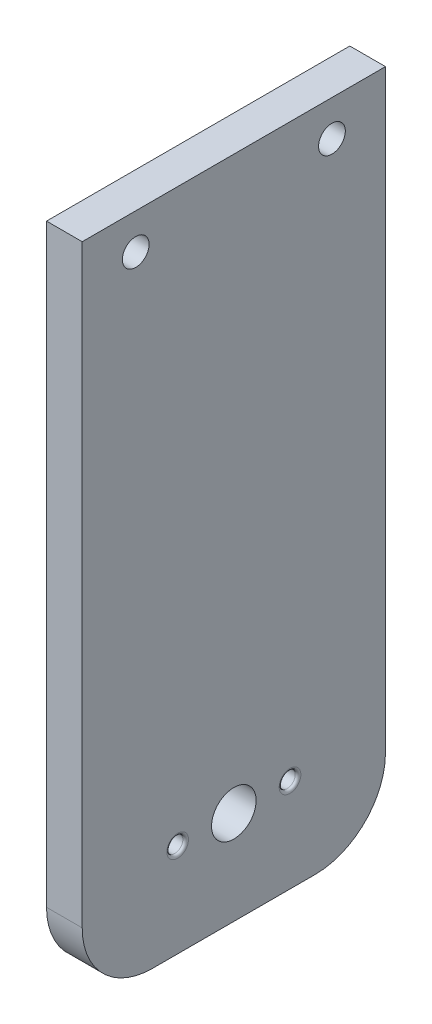
SolidWorks part; units mm, degrees
material "Plain Carbon Steel"
ref_plane "Front Plane" through (0, 0, 0) normal (0, 0, 1) x (1, 0, 0)
ref_plane "Top Plane" through (0, 0, 0) normal (0, 1, 0) x (1, 0, 0)
ref_plane "Right Plane" through (0, 0, 0) normal (1, 0, 0) x (0, 0, -1)
sketch "Sketch1" plane through (0, 0, 0) normal (1, 0, 0) x (0, 0, -1)
  line L0 (-53.975, -84.9275) -> (53.975, -84.9275) construction
  line L1 (-53.975, 118.2675) -> (53.975, 118.2675)
  line L2 (-53.975, 118.2675) -> (-53.975, -118.2675)
  line L3 (-53.975, -118.2675) -> (53.975, -118.2675)
  line L4 (53.975, 118.2675) -> (53.975, -118.2675)
  line L5 (-53.975, 118.2675) -> (53.975, -118.2675) construction
  line L6 (-53.975, -118.2675) -> (53.975, 118.2675) construction
  line L7 (-53.975, 105.5675) -> (53.975, 105.5675) construction
  line L8 (-34.925, 105.5675) -> (-34.925, 110.33) construction
  line L9 (34.925, 105.5675) -> (34.925, 110.33) construction
  line L10 (-53.975, 105.5675) -> (-34.925, 105.5675) construction
  line L11 (34.925, 105.5675) -> (53.975, 105.5675) construction
  circle A0 centre (0, -84.9275) radius 7.94
  circle A1 centre (20, -84.9275) radius 2.86
  circle A2 centre (-20, -84.9275) radius 2.86
  circle A3 centre (-34.925, 105.5675) radius 4.7625
  circle A4 centre (34.925, 105.5675) radius 4.7625
  point P0 (0, 0)
  point P20 (0, 0)
  point P23 (0, 0)
  dimension "D4" = 15.88
  dimension "D6" = 5.72
  dimension "D7" = 5.72
  dimension "D9" = 9.525
  dimension "D1" = 236.535
  dimension "D2" = 107.95
  dimension "D3" = 33.34
  dimension "D5" = 20
  dimension "D8" = 20
  dimension " 1in/2" = 12.7
  dimension "D10" = 19.05
  dimension "D11" = 19.05
extrude "Boss-Extrude1" add sketch "Sketch1" along normal blind 12.7
fillet "Fillet1" radius 25 2 edges at (6.35, -118.2675, 53.975) (6.35, -118.2675, -53.975)
fillet "Fillet2" radius 1 4 edges at (12.7, -84.9275, -22.86) (0, -84.9275, -22.86) (12.7, -84.9275, 17.14) (0, -84.9275, 17.14)
